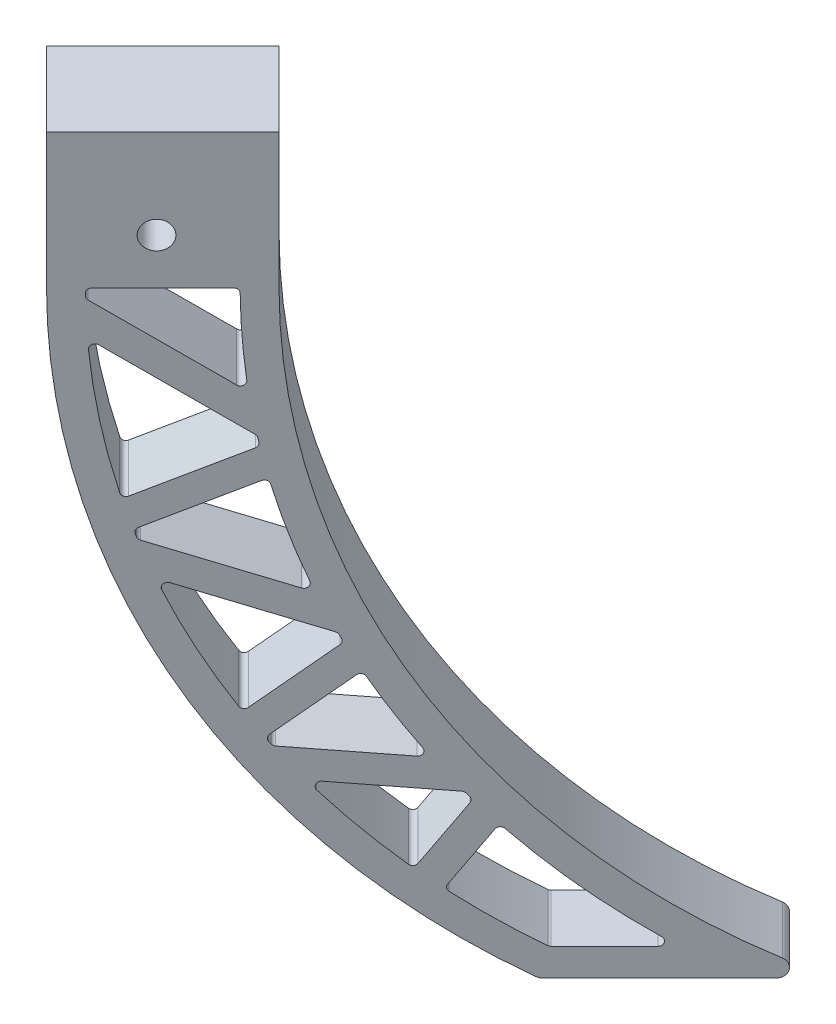
SolidWorks part; units mm, degrees
ref_plane "Front Plane" through (0, 0, 0) normal (0, 0, 1) x (1, 0, 0)
ref_plane "Top Plane" through (0, 0, 0) normal (0, 1, 0) x (1, 0, 0)
ref_plane "Right Plane" through (0, 0, 0) normal (1, 0, 0) x (0, 0, -1)
ref_plane "Plane1" through (50.5423, 0, -50.5423) normal (-0.7071, 0, 0.7071) x (0.7071, 0, 0.7071)
ref_plane "Plane2" through (61.1489, 0, -61.1489) normal (-0.7071, 0, 0.7071) x (0.7071, 0, 0.7071)
sketch "Sketch1" plane through (61.1489, 0, -61.1489) normal (-0.7071, 0, 0.7071) x (0.7071, 0, 0.7071)
  line L0 (-8, -81.9015) -> (-8, -78.9015) construction
  line L1 (-8, -78.9015) -> (4, -78.9015) construction
  line L2 (4, -78.9015) -> (4, -92.9015) construction
  line L3 (-4, -84.2109) -> (-8, -81.9015) construction
  line L4 (-4, -92.9015) -> (-4, -84.2109) construction
  line L5 (-8, -81.9015) -> (-8, -78.9015) construction
  line L6 (-8, -78.9015) -> (4, -78.9015) construction
  line L7 (4, -78.9015) -> (4, -92.9015) construction
  line L8 (-4, -84.2109) -> (-8, -81.9015) construction
  line L9 (-4, -92.9015) -> (-4, -84.2109) construction
  line L10 (-3.75, -92.9015) -> (-3.75, -84.0666)
  line L11 (-3.75, -84.0666) -> (-7.75, -81.7572)
  line L12 (-7.75, -81.7572) -> (-7.75, -79.1515)
  line L13 (-7.75, -79.1515) -> (3.75, -79.1515)
  line L14 (3.75, -79.1515) -> (3.75, -92.9015)
  line L15 (-3.75, -92.9015) -> (-3.75, -159.1515)
  line L16 (3.75, -92.9015) -> (3.75, -159.1515)
  line L17 (3.75, -159.1515) -> (-3.75, -159.1515)
  dimension "D2" = 80
  dimension "D1" = 0.25
extrude "Boss-Extrude1" add sketch "Sketch1" along normal blind 40 and the other way blind 40
sketch "Sketch2" plane through (-2.6517, 0, -2.6517) normal (-0.7071, 0, -0.7071) x (-0.7071, 0, 0.7071)
  line L0 (-83.5847, -79.1515) -> (-83.5847, -93.9015)
  line L1 (-126.4776, -79.1515) -> (-46.4776, -79.1515) construction
  line L2 (-83.5847, -78.9015) -> (-83.5847, -81.9015) construction
  line L6 (-83.8177, -93.9015) -> (-83.3691, -93.9015) construction
  line L7 (-65.6347, -93.9015) -> (-65.6347, -79.1515)
  line L10 (-126.4776, -159.1515) -> (-46.4776, -159.1515) construction
  line L11 (-126.4776, -159.1515) -> (-126.4776, -79.1515)
  line L12 (-126.4776, -79.1515) -> (-83.5847, -79.1515)
  line L13 (-65.6347, -79.1515) -> (-46.4776, -79.1515)
  line L14 (-46.4776, -79.1515) -> (-46.4776, -159.1515)
  line L15 (-46.4776, -159.1515) -> (-103.6558, -159.1515)
  arc A0 (-83.5847, -93.9015) -> (-126.4776, -159.1515) centre (-154.6613, -93.9015) cw
  arc A1 (-65.6347, -93.9015) -> (-103.6558, -159.1515) centre (-140.6347, -93.9015) cw
  dimension "D1" = 75
  dimension "D2" = 17.95
extrude "Cut-Extrude1" cut sketch "Sketch2" against normal through all and the other way blind 30
sketch "Sketch3" plane through (2.6517, 0, 2.6517) normal (0.7071, 0, 0.7071) x (0.7071, 0, -0.7071)
  circle A0 centre (74.1282, -88.9015) radius 1.5
extrude "Cut-Extrude2" cut sketch "Sketch3" against normal through all
fillet "Fillet1" radius 1 2 edges at (73.2957, -159.1515, -73.2957) (89.4331, -159.1515, -89.4331)
sketch "Sketch4" plane through (-2.6517, 0, -2.6517) normal (-0.7071, 0, -0.7071) x (-0.7071, 0, 0.7071)
  line L1 (-68.6347, -93.9015) -> (-80.5847, -93.9015)
  line L2 (-104.4555, -156.1515) -> (-114.5081, -156.1515)
  line L3 (-104.4555, -156.1515) -> (-114.5081, -156.1515) construction
  line L4 (-68.6416, -94.9015) -> (-81.2385, -103.722)
  line L5 (-81.9107, -107.855) -> (-68.7928, -98.6696)
  line L6 (-82.1097, -108.855) -> (-71.4468, -113.8272)
  line L7 (-82.7913, -111.8472) -> (-72.3456, -116.7182)
  line L8 (-72.6691, -117.6644) -> (-86.3951, -122.6602)
  line L9 (-74.0806, -121.3707) -> (-88.1364, -126.4866)
  line L10 (-88.5824, -127.3817) -> (-80.784, -133.9252)
  line L11 (-90.0246, -130.0877) -> (-82.5101, -136.3931)
  line L12 (-83.1059, -137.1963) -> (-95.3394, -138.2666)
  line L13 (-114.5081, -156.1515) -> (-104.4555, -156.1515)
  line L14 (-97.903, -141.5023) -> (-85.6917, -140.434)
  line L15 (-98.5507, -142.2642) -> (-94.0024, -148.7598)
  line L16 (-100.6093, -144.5545) -> (-96.3344, -150.6597)
  line L17 (-104.4555, -156.1515) -> (-101.2356, -156.1926)
  arc A4 (-80.5847, -93.9015) -> (-81.2385, -103.722) centre (-154.6614, -93.9015) cw
  arc A5 (-68.6347, -93.9015) -> (-68.6416, -94.9015) centre (-140.6347, -93.9015) cw
  arc A6 (-81.9107, -107.855) -> (-82.1097, -108.855) centre (-154.6613, -93.9015) cw
  arc A7 (-68.7928, -98.6696) -> (-71.4468, -113.8272) centre (-140.6347, -93.9015) cw
  arc A8 (-104.4555, -156.1515) -> (-68.6347, -93.9015) centre (-140.6347, -93.9015) ccw
  arc A9 (-114.5081, -156.1515) -> (-80.5847, -93.9015) centre (-154.6613, -93.9015) ccw
  arc A10 (-104.4555, -156.1515) -> (-96.3344, -150.6597) centre (-140.6347, -93.9015) ccw construction
  arc A11 (-114.5081, -156.1515) -> (-100.6093, -144.5545) centre (-154.6613, -93.9015) ccw construction
  arc A12 (-72.3456, -116.7182) -> (-72.6691, -117.6644) centre (-140.6347, -93.9015) cw
  arc A13 (-82.7913, -111.8472) -> (-86.3951, -122.6602) centre (-154.6613, -93.9015) cw
  arc A14 (-86.3951, -122.6602) -> (-80.5847, -93.9015) centre (-154.6613, -93.9015) ccw construction
  arc A15 (-88.1364, -126.4866) -> (-95.3394, -138.2666) centre (-154.6613, -93.9015) cw
  arc A16 (-72.6691, -117.6644) -> (-68.6347, -93.9015) centre (-140.6347, -93.9015) ccw construction
  arc A17 (-74.0806, -121.3707) -> (-83.1059, -137.1963) centre (-140.6347, -93.9015) cw
  arc A18 (-95.3394, -138.2666) -> (-88.1364, -126.4866) centre (-154.6613, -93.9015) ccw construction
  arc A19 (-97.903, -141.5023) -> (-98.5507, -142.2642) centre (-154.6613, -93.9015) cw
  arc A20 (-83.1059, -137.1963) -> (-74.0806, -121.3707) centre (-140.6347, -93.9015) ccw construction
  arc A21 (-85.6917, -140.434) -> (-94.0024, -148.7598) centre (-140.6347, -93.9015) cw
  arc A22 (-98.5507, -142.2642) -> (-97.903, -141.5023) centre (-154.6613, -93.9015) ccw construction
  arc A23 (-100.6093, -144.5545) -> (-114.5081, -156.1515) centre (-154.6613, -93.9015) cw
  arc A24 (-94.0024, -148.7598) -> (-85.6917, -140.434) centre (-140.6347, -93.9015) ccw construction
  arc A25 (-96.3344, -150.6597) -> (-104.4555, -156.1515) centre (-140.6347, -93.9015) cw
  dimension "D2" = 3
  dimension "D3" = 3
  dimension "D4" = 3
  dimension "D5" = 3
  dimension "D6" = 3
  dimension "D7" = 1
  dimension "D8" = 1
  dimension "D9" = 35
  dimension "D10" = 60
  dimension "D11" = 45
  dimension "D12" = 1
  dimension "D13" = 1
  dimension "D14" = 60
  dimension "D15" = 1
  dimension "D16" = 45
  dimension "D17" = 1
  dimension "D18" = 3
  dimension "D19" = 60
  dimension "D1" = 3
extrude "Cut-Extrude3" cut sketch "Sketch4" against normal blind 40 contours A25 L16 A23 L13 | A21 L14 A19 L15 | A17 L11 A15 L12 | A17 L9 A15 L10 | L7 A13 L8 A12 | A7 L5 A6 L6 | A5 L1 A4 L4 region at (51.3436, -97.1801, -56.6469) region at (49.7717, -106.9652, -55.075) region at (54.0139, -117.2294, -59.3172) region at (54.7272, -127.4049, -60.0305) region at (60.2917, -135.1435, -65.595) region at (62.9311, -143.6501, -68.2344) region at (70.8176, -151.6831, -76.1209)
fillet "Fillet2" radius 0.5 28 edges at (80.9694, -156.1515, -80.9694) (71.1415, -144.5545, -71.1415) (68.1187, -150.6597, -68.1187) (73.8612, -156.1515, -73.8612) (66.4697, -148.7598, -66.4697) (60.5932, -140.434, -60.5932) (69.2279, -141.5023, -69.2279) (69.6859, -142.2642, -69.6859) (67.4151, -138.2666, -67.4151) (63.657, -130.0877, -63.657) (58.3435, -136.3931, -58.3435) (58.7647, -137.1963, -58.7647) (57.1229, -133.9252, -57.1229) (52.3829, -121.3707, -52.3829) (62.3219, -126.4866, -62.3219) (62.6372, -127.3817, -62.6372) (61.0905, -122.6602, -61.0905) (58.5423, -111.8472, -58.5423) (51.1561, -116.7182, -51.1561) (51.3848, -117.6644, -51.3848) (50.5205, -113.8272, -50.5205) (48.6438, -98.6696, -48.6438) (57.9196, -107.855, -57.9196) (58.0603, -108.855, -58.0603) (57.4443, -103.722, -57.4443) (56.982, -93.9015, -56.982) (48.537, -94.9015, -48.537) (48.5321, -93.9015, -48.5321)
